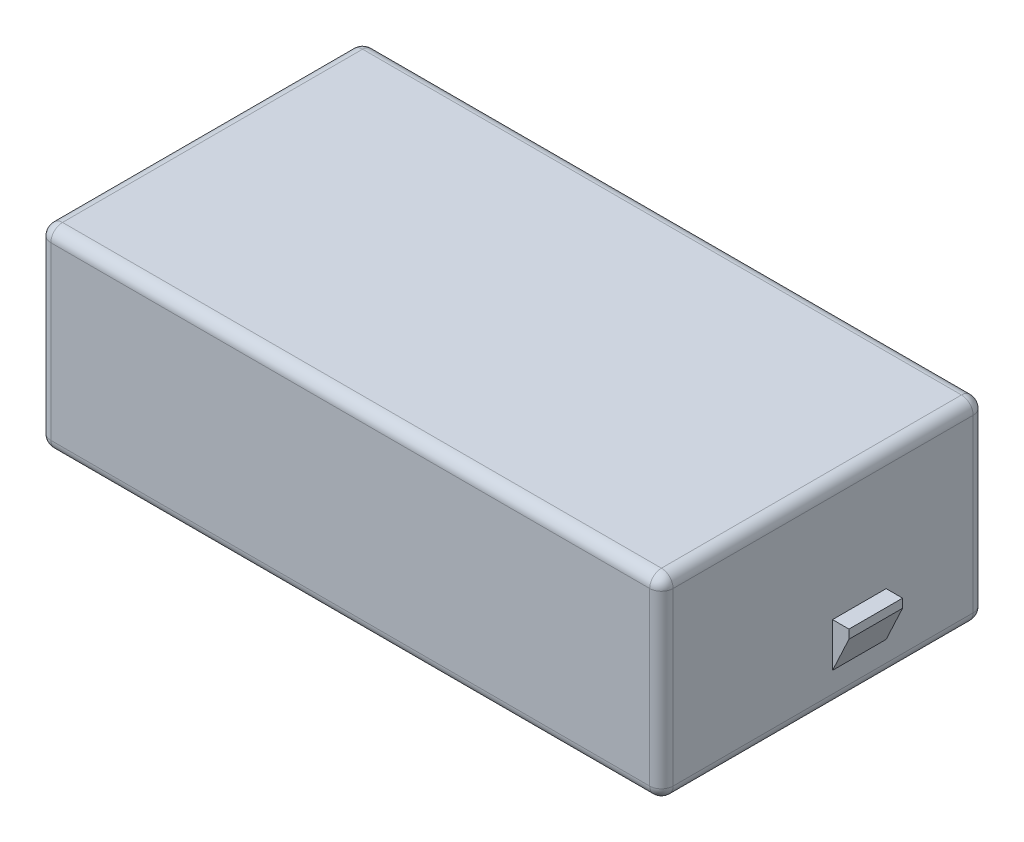
SolidWorks part; units mm, degrees
ref_plane "Piano frontale" through (0, 0, 0) normal (0, 0, 1) x (1, 0, 0)
ref_plane "Piano superiore" through (0, 0, 0) normal (0, 1, 0) x (1, 0, 0)
ref_plane "Piano destro" through (0, 0, 0) normal (1, 0, 0) x (0, 0, -1)
sketch "Schizzo1" plane through (0, 0, 0) normal (0, 0, 1) x (1, 0, 0)
  line L1 (-51.2357, 27.8668) -> (54.9643, 27.8668)
  line L2 (-51.2357, 27.8668) -> (-51.2357, -5.3332)
  line L3 (-51.2357, -5.3332) -> (54.9643, -5.3332)
  line L4 (54.9643, 27.8668) -> (54.9643, -5.3332)
  dimension "D1" = 106.2
  dimension "D2" = 33.2
extrude "Estrusione-Estrusione1" add sketch "Schizzo1" along normal blind 55.2 contours L1 L4 L3 L2
fillet "Raccordo1" radius 2 12 edges at (54.9643, 11.2668, 55.2) (54.9643, -5.3332, 27.6) (54.9643, 27.8668, 27.6) (54.9643, 11.2668, 0) (1.8643, -5.3332, 0) (1.8643, 27.8668, 0) (-51.2357, 11.2668, 0) (-51.2357, -5.3332, 27.6) (-51.2357, 27.8668, 27.6) (-51.2357, 11.2668, 55.2) (1.8643, -5.3332, 55.2) (1.8643, 27.8668, 55.2)
sketch "Schizzo2" plane through (-51.2357, 0, 0) normal (-1, 0, 0) x (0, 0, 1)
  line L0 (2, 25.8668) -> (2, -3.3332) construction
  line L1 (36, 19.6668) -> (48, 19.6668)
  line L2 (36, 19.6668) -> (36, 6.6668)
  line L3 (36, 6.6668) -> (48, 6.6668)
  line L4 (48, 19.6668) -> (48, 6.6668)
  line L5 (2, -3.3332) -> (53.2, -3.3332) construction
  dimension "D1" = 12
  dimension "D2" = 13
  dimension "D3" = 46
  dimension "D4" = 23
extrude "Estrusione-Estrusione2" add sketch "Schizzo2" along normal blind 6
chamfer "Smusso1" distance 6 distance2 10 1 edges at (-57.2357, 6.6668, 42) first distance on face at (-54.2357, 6.6668, 42)
sketch "Schizzo4" plane through (54.9643, 0, 0) normal (1, 0, 0) x (0, 0, -1)
  line L1 (-26, 7.6668) -> (-16.85, 7.6668)
  line L2 (-26, 7.6668) -> (-26, 0.1668)
  line L3 (-26, 0.1668) -> (-16.85, 0.1668)
  line L4 (-16.85, 7.6668) -> (-16.85, 0.1668)
  line L5 (-53.2, -3.3332) -> (-2, -3.3332) construction
  line L6 (-2, -3.3332) -> (-2, 25.8668) construction
  dimension "D1" = 9.15
  dimension "D2" = 7.5
  dimension "D3" = 11
  dimension "D4" = 24
extrude "Estrusione-Estrusione3" add sketch "Schizzo4" along normal blind 2.8
chamfer "Smusso2" distance 2.8 distance2 6 1 edges at (57.7643, 0.1668, 21.425) first distance on face at (56.3643, 0.1668, 21.425)
sketch "Schizzo5" plane through (0, 0, 0) normal (0, 0, -1) x (-1, 0, 0)
  line L1 (19.2357, 23.8668) -> (44.6357, 23.8668)
  line L2 (19.2357, 23.8668) -> (19.2357, 7.8668)
  line L3 (19.2357, 7.8668) -> (44.6357, 7.8668)
  line L4 (44.6357, 23.8668) -> (44.6357, 7.8668)
  line L5 (49.2357, 25.8668) -> (-52.9643, 25.8668) construction
  line L6 (49.2357, -3.3332) -> (49.2357, 25.8668) construction
  dimension "D1" = 25.4
  dimension "D2" = 16
  dimension "D3" = 18
  dimension "D4" = 30
extrude "Estrusione-Estrusione4" add sketch "Schizzo5" along normal blind 2.5
